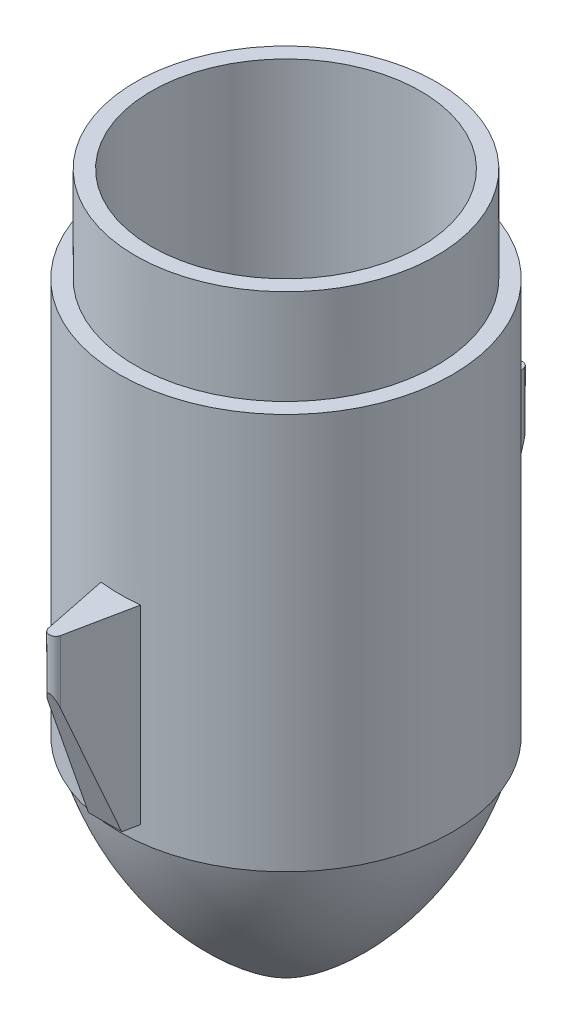
SolidWorks part; units mm, degrees
ref_plane "Front Plane" through (0, 0, 0) normal (0, 0, 1) x (1, 0, 0)
ref_plane "Top Plane" through (0, 0, 0) normal (0, 1, 0) x (1, 0, 0)
ref_plane "Right Plane" through (0, 0, 0) normal (1, 0, 0) x (0, 0, -1)
sketch "Sketch1" plane through (0, 0, 0) normal (0, 1, 0) x (1, 0, 0)
  circle A2 centre (0, 0) radius 42.5
  dimension "D1" = 85
extrude "Boss-Extrude2" add sketch "Sketch1" along normal blind 150 contours A2
shell "Shell1" thickness 5 removed face at (0, 150, 42.5) outward yes
sketch "Sketch2" plane through (0, -5, 0) normal (0, -1, 0) x (-1, 0, 0)
  circle A0 centre (0, 0) radius 47.5
  circle A1 centre (0, 0) radius 52.5
  dimension "D1" = 105
  dimension "D2" = 95
extrude "Boss-Extrude3" add sketch "Sketch2" against normal blind 125
sketch "Sketch3" plane through (0, 0, 0) normal (0, 0, 1) x (1, 0, 0)
  line L0 (0, 0) -> (0, -70)
  line L1 (0, 0) -> (-52.5, 0)
  line L2 (-52.5, 120) -> (-52.5, -5) construction
  arc A0 (0, -70) -> (-52.5, 0) centre (46.7993, 19.787) cw
revolve "Revolve1" add sketch "Sketch3" angle 360 about L0
ref_plane "Plane1" through (0, 60, 0) normal (0, 1, 0) x (1, 0, 0)
sketch "Sketch4" plane through (0, 60, 0) normal (0, 1, 0) x (1, 0, 0)
  line L0 (0, 0) -> (0, 117.9355) construction
  line L1 (6.2454, 52.1272) -> (1.9616, 73.1213)
  line L2 (-6.2454, 52.1272) -> (-1.9616, 73.1213)
  circle A0 centre (0, 0) radius 52.5 construction
  arc A1 (1.9616, 73.1213) -> (-1.9616, 73.1213) centre (0, 72.6518) ccw
  arc A2 (6.2454, 52.1272) -> (-6.2454, 52.1272) centre (0, 0) ccw
extrude "Boss-Extrude4" add sketch "Sketch4" against normal blind 60
sketch "Sketch5" plane through (0, 0, 0) normal (1, 0, 0) x (0, 0, -1)
  line L0 (74.6687, 43.9407) -> (56.0242, -2.6223)
  line L1 (74.6687, 0) -> (74.6687, 60) construction
  line L2 (56.0242, -2.6223) -> (78.7969, -2.6223)
  line L3 (78.7969, -2.6223) -> (78.7969, 43.9407)
  line L4 (78.7969, 43.9407) -> (74.6687, 43.9407)
extrude "Cut-Extrude1" cut sketch "Sketch5" against normal mid plane 15
pattern_circular "CirPattern1" count 2 over 360 about axis through (0, 120, 0) along (0, -1, 0) of "Boss-Extrude4" reverse direction yes
pattern_circular "CirPattern2" count 2 over 360 about axis through (0, 120, 0) along (0, -1, 0) of "Cut-Extrude1" reverse direction yes
